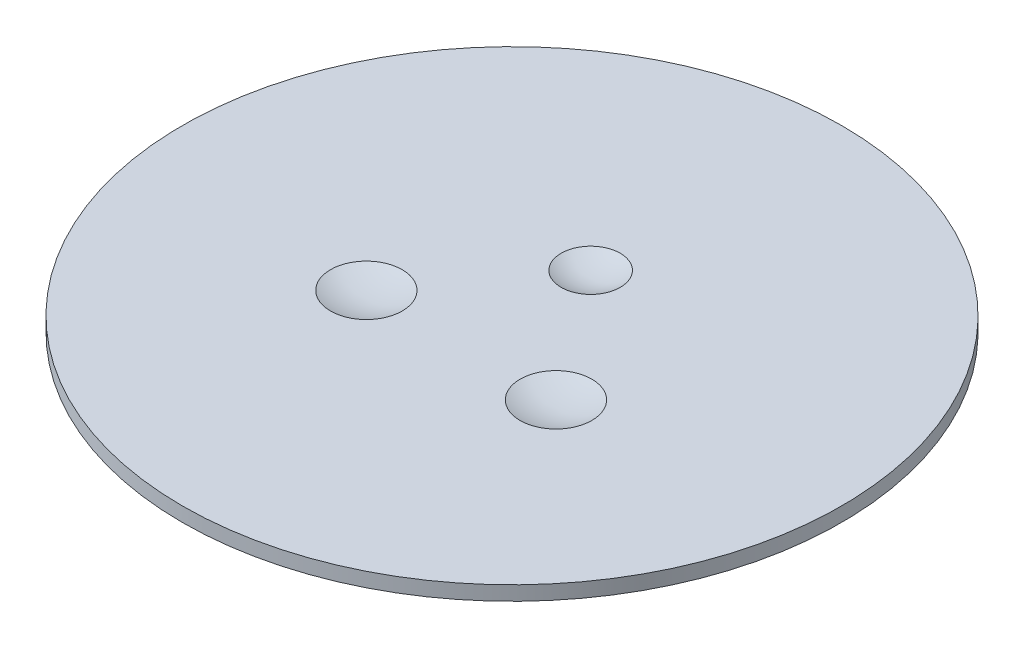
SolidWorks part; units mm, degrees
material "7075-T6 (SN)"
ref_plane "Front Plane" through (0, 0, 0) normal (0, 0, 1) x (1, 0, 0)
ref_plane "Top Plane" through (0, 0, 0) normal (0, 1, 0) x (1, 0, 0)
ref_plane "Right Plane" through (0, 0, 0) normal (1, 0, 0) x (0, 0, -1)
sketch "Sketch1" plane through (0, 0, 0) normal (0, 1, 0) x (1, 0, 0)
  line L0 (-330.835, -177.3911) -> (0, 0) construction
  line L1 (-330.835, -177.3911) -> (330.835, -177.3911) construction
  line L2 (330.835, -177.3911) -> (0, 274.5232) construction
  line L3 (0, 274.5232) -> (-330.835, -177.3911) construction
  line L4 (0, 0) -> (330.835, -177.3911) construction
  circle A1 centre (0, 0) radius 1150
  dimension "D1" = 2300
  dimension "D2" = 661.67
  dimension "D3" = 560.07
  dimension "D4" = 560.07
  dimension "D5" = 177.3911
extrude "Boss-Extrude1" add sketch "Sketch1" along normal blind 50
ref_plane "Plane1" through (0, 0, 177.3911) normal (0, 0, 1) x (1, 0, 0)
sketch "Sketch3" plane through (0, 0, 177.3911) normal (0, 0, 1) x (1, 0, 0)
  line L0 (1150, 50) -> (-1150, 50) construction
  line L2 (457.5865, 50) -> (455.8977, 50)
  line L3 (-457.5865, 50) -> (-457.5865, 50.6966)
  line L4 (0, -1265) -> (0, 1265) construction
  line L5 (-205.7723, 50) -> (-330.835, 50)
  line L6 (457.5865, 50) -> (457.5865, 50.6966)
  line L7 (-330.835, 25.4) -> (-330.835, 50)
  line L8 (-455.8977, 50) -> (-457.5865, 50)
  line L9 (330.835, 50) -> (330.835, 25.4)
  line L10 (330.835, 50) -> (205.7723, 50)
  arc A0 (-457.5865, 50.6966) -> (-455.8977, 50) centre (-330.835, 355.6) ccw
  arc A1 (457.5865, 50.6966) -> (455.8977, 50) centre (330.835, 355.6) cw
  arc A2 (-330.835, 25.4) -> (-205.7723, 50) centre (-330.835, 355.6) ccw
  arc A3 (330.835, 25.4) -> (205.7723, 50) centre (330.835, 355.6) cw
  point P0 (330.835, 0)
  point P2 (-330.835, 0)
  dimension "D1" = 660.4
  dimension "D2" = 355.6
revolve "Cut-Revolve2" cut sketch "Sketch3" angle 360 about L7 region at (-283.6944, 40.1279, 177.3911)
revolve "Cut-Revolve3" cut sketch "Sketch3<4>" angle 360 about L9
sketch "Sketch3<4>" plane through (0, 0, 177.3911) normal (0, 0, 1) x (1, 0, 0) same geometry as "Sketch3"
ref_plane "Plane2" through (0, 0, -274.5232) normal (0, 0, 1) x (1, 0, 0)
sketch "Sketch6" plane through (0, 0, -274.5232) normal (0, 0, 1) x (1, 0, 0)
  line L0 (1150, 50) -> (-1150, 50) construction
  line L1 (103.1599, 50) -> (0, 50)
  line L2 (0, 25.4) -> (0, 50)
  arc A0 (0, 25.4) -> (103.1599, 50) centre (0, 254) ccw
  point P0 (0, 0)
  point P6 (0, 25.4)
  dimension "D1" = 457.2
revolve "Cut-Revolve4" cut sketch "Sketch6" angle 360 about L2 region at (38.9785, 40.1132, -274.5232)
ref_plane "Plane3" through (0, 50.6966, 0) normal (0, 1, 0) x (1, 0, 0)
